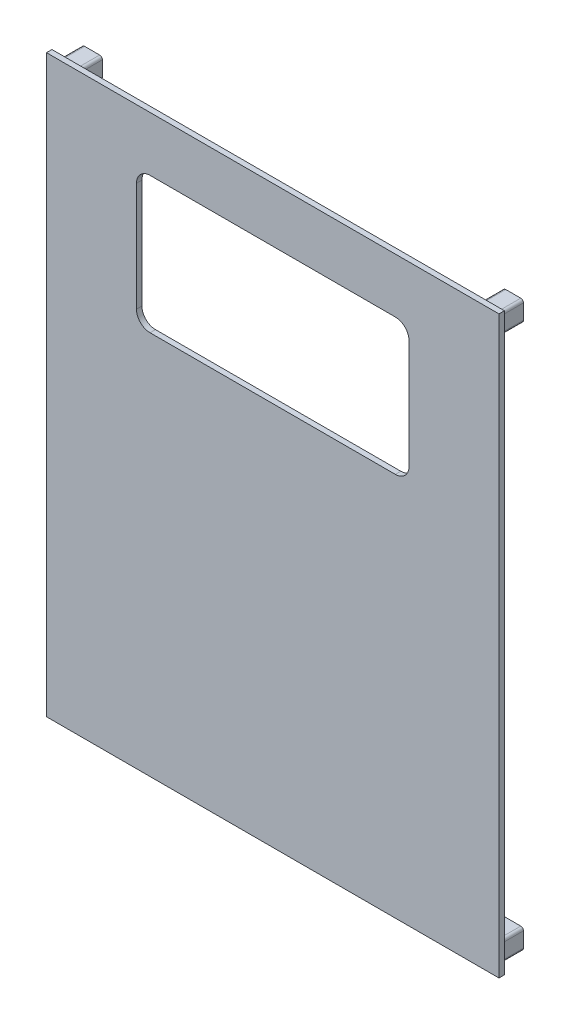
SolidWorks part; units mm, degrees
ref_plane "Front Plane" through (0, 0, 0) normal (0, 0, 1) x (1, 0, 0)
ref_plane "Top Plane" through (0, 0, 0) normal (0, 1, 0) x (1, 0, 0)
ref_plane "Right Plane" through (0, 0, 0) normal (1, 0, 0) x (0, 0, -1)
sketch "Sketch1" plane through (0, 0, 0) normal (0, 0, 1) x (1, 0, 0)
  line L4 (48, 73.2573) -> (48, -16.7427)
  line L5 (55, -23.7427) -> (105, -23.7427)
  line L6 (112, -16.7427) -> (112, 73.2573)
  line L7 (105, 80.2573) -> (55, 80.2573)
  line L8 (53, 73.2573) -> (53, -16.7427)
  line L9 (55, -18.7427) -> (105, -18.7427)
  line L10 (107, -16.7427) -> (107, 73.2573)
  line L11 (105, 75.2573) -> (55, 75.2573)
  arc A4 (48, -16.7427) -> (55, -23.7427) centre (55, -16.7427) ccw
  arc A5 (105, -23.7427) -> (112, -16.7427) centre (105, -16.7427) ccw
  arc A6 (112, 73.2573) -> (105, 80.2573) centre (105, 73.2573) ccw
  arc A7 (55, 80.2573) -> (48, 73.2573) centre (55, 73.2573) ccw
  arc A8 (53, -16.7427) -> (55, -18.7427) centre (55, -16.7427) ccw
  arc A9 (105, -18.7427) -> (107, -16.7427) centre (105, -16.7427) ccw
  arc A10 (107, 73.2573) -> (105, 75.2573) centre (105, 73.2573) ccw
  arc A11 (55, 75.2573) -> (53, 73.2573) centre (55, 73.2573) ccw
  dimension "D1" = 5
extrude "Boss-Extrude1" add sketch "Sketch1" against normal blind 3
sketch "Sketch2" plane through (0, 0, 0) normal (0, 0, 1) x (1, 0, 0)
  line L0 (-3, -127.7573) -> (163, -127.7573)
  line L1 (80, 83.2573) -> (80, -121.7427) construction
  line L3 (30, 63.2573) -> (130, 63.2573)
  line L6 (30, 63.2573) -> (30, 13.2573)
  line L9 (163, -127.7573) -> (163, 83.2573)
  line L10 (163, 83.2573) -> (-3, 83.2573)
  line L11 (-3, 83.2573) -> (-3, -127.7573)
  line L12 (30, 13.2573) -> (130, 13.2573)
  line L13 (130, 63.2573) -> (130, 13.2573)
extrude "Boss-Extrude2" add sketch "Sketch2" along normal blind 3
sketch "Sketch3" plane through (0, 0, -3) normal (0, 0, -1) x (-1, 0, 0)
  line L4 (-55, 80.2573) -> (-105, 80.2573)
  line L5 (-112, 73.2573) -> (-112, -16.7427)
  line L6 (-105, -23.7427) -> (-55, -23.7427)
  line L7 (-48, -16.7427) -> (-48, 73.2573)
  line L8 (-55, 80.2573) -> (-105, 80.2573)
  line L9 (-112, 73.2573) -> (-112, -16.7427)
  line L10 (-105, -23.7427) -> (-55, -23.7427)
  line L11 (-48, -16.7427) -> (-48, 73.2573)
  arc A4 (-48, 73.2573) -> (-55, 80.2573) centre (-55, 73.2573) ccw
  arc A5 (-105, 80.2573) -> (-112, 73.2573) centre (-105, 73.2573) ccw
  arc A6 (-112, -16.7427) -> (-105, -23.7427) centre (-105, -16.7427) ccw
  arc A7 (-55, -23.7427) -> (-48, -16.7427) centre (-55, -16.7427) ccw
  arc A8 (-48, 73.2573) -> (-55, 80.2573) centre (-55, 73.2573) ccw
  arc A9 (-105, 80.2573) -> (-112, 73.2573) centre (-105, 73.2573) ccw
  arc A10 (-112, -16.7427) -> (-105, -23.7427) centre (-105, -16.7427) ccw
  arc A11 (-55, -23.7427) -> (-48, -16.7427) centre (-55, -16.7427) ccw
  dimension "D1" = 0
extrude "Cut-Extrude1" cut sketch "Sketch3" against normal up to surface (3 mm away) up to face at (80, -22.25, 0)
fillet "Fillet1" radius 5 4 edges at (30, 63.2573, 1.5) (30, 13.2573, 1.5) (130, 13.2573, 1.5) (130, 63.2573, 1.5)
sketch "Sketch4" plane through (0, 0, 3) normal (0, 0, 1) x (1, 0, 0)
  line L4 (6.5, 81.2573) -> (-1, 81.2573)
  line L5 (6.5, 73.7573) -> (6.5, 81.2573)
  line L6 (-1, 73.7573) -> (6.5, 73.7573)
  line L7 (-1, 81.2573) -> (-1, 73.7573)
  line L8 (6.5, 81.2573) -> (-1, 81.2573)
  line L9 (6.5, 73.7573) -> (6.5, 81.2573)
  line L10 (-1, 73.7573) -> (6.5, 73.7573)
  line L11 (-1, 81.2573) -> (-1, 73.7573)
  line L12 (153.5, -125.7573) -> (161, -125.7573)
  line L13 (153.5, -118.2573) -> (153.5, -125.7573)
  line L14 (161, -118.2573) -> (153.5, -118.2573)
  line L15 (161, -125.7573) -> (161, -118.2573)
  line L16 (153.5, -125.7573) -> (161, -125.7573)
  line L17 (153.5, -118.2573) -> (153.5, -125.7573)
  line L18 (161, -118.2573) -> (153.5, -118.2573)
  line L19 (161, -125.7573) -> (161, -118.2573)
  line L20 (-1, -125.7573) -> (6.5, -125.7573)
  line L21 (6.5, -125.7573) -> (6.5, -118.2573)
  line L22 (6.5, -118.2573) -> (-1, -118.2573)
  line L23 (-1, -118.2573) -> (-1, -125.7573)
  line L24 (-1, -125.7573) -> (6.5, -125.7573)
  line L25 (6.5, -125.7573) -> (6.5, -118.2573)
  line L26 (6.5, -118.2573) -> (-1, -118.2573)
  line L27 (-1, -118.2573) -> (-1, -125.7573)
  line L28 (161, 81.2573) -> (153.5, 81.2573)
  line L29 (161, 73.7573) -> (161, 81.2573)
  line L30 (153.5, 73.7573) -> (161, 73.7573)
  line L31 (153.5, 81.2573) -> (153.5, 73.7573)
  line L32 (161, 81.2573) -> (153.5, 81.2573)
  line L33 (161, 73.7573) -> (161, 81.2573)
  line L34 (153.5, 73.7573) -> (161, 73.7573)
  line L35 (153.5, 81.2573) -> (153.5, 73.7573)
  dimension "D1" = 0
  dimension "D2" = 0
  dimension "D3" = 0
  dimension "D4" = 0
extrude "Boss-Extrude3" add sketch "Sketch4" against normal blind 11
fillet "Fillet2" radius 1 16 edges at (161, -118.2573, -4) (153.5, -118.2573, -4) (161, -125.7573, -4) (153.5, -125.7573, -4) (6.5, -125.7573, -4) (-1, -125.7573, -4) (6.5, -118.2573, -4) (-1, -118.2573, -4) (-1, 73.7573, -4) (-1, 81.2573, -4) (6.5, 81.2573, -4) (6.5, 73.7573, -4) (153.5, 73.7573, -4) (161, 73.7573, -4) (153.5, 81.2573, -4) (161, 81.2573, -4)
sketch "Sketch5" plane through (0, 0, -8) normal (0, 0, -1) x (-1, 0, 0)
  circle A0 centre (-157.25, 77.5073) radius 1.6
  circle A1 centre (-2.75, 77.5073) radius 1.6
  circle A2 centre (-2.75, -122.0073) radius 1.6
  circle A3 centre (-157.25, -122.0073) radius 1.6
extrude "Cut-Extrude2" cut sketch "Sketch5" against normal blind 5
sketch "Sketch6" plane through (0, 0, -8) normal (0, 0, -1) x (-1, 0, 0)
  circle A0 centre (-157.25, 77.5073) radius 2.25
  circle A1 centre (-2.75, 77.5073) radius 2.25
  circle A2 centre (-157.25, -122.0073) radius 2.25
  circle A3 centre (-2.75, -122.0073) radius 2.25
extrude "Cut-Extrude3" cut sketch "Sketch6" against normal blind 3
sketch "Sketch7" plane through (0, 0, 0) normal (0, 0, -1) x (-1, 0, 0)
  line L4 (3, -127.7573) -> (3, 83.2573)
  line L5 (3, 83.2573) -> (-163, 83.2573)
  line L6 (-163, 83.2573) -> (-163, -127.7573)
  line L7 (-163, -127.7573) -> (3, -127.7573)
  line L8 (3, -127.7573) -> (3, 83.2573)
  line L9 (3, 83.2573) -> (-163, 83.2573)
  line L10 (-163, 83.2573) -> (-163, -127.7573)
  line L11 (-163, -127.7573) -> (3, -127.7573)
  line L12 (-160, 73.7573) -> (-154.5, 73.7573)
  line L13 (-153.5, 74.7573) -> (-153.5, 80.2573)
  line L14 (-154.5, 81.2573) -> (-160, 81.2573)
  line L15 (-161, 80.2573) -> (-161, 74.7573)
  line L16 (-160, 73.7573) -> (-154.5, 73.7573)
  line L17 (-153.5, 74.7573) -> (-153.5, 80.2573)
  line L18 (-154.5, 81.2573) -> (-160, 81.2573)
  line L19 (-161, 80.2573) -> (-161, 74.7573)
  line L20 (-5.5, 73.7573) -> (0, 73.7573)
  line L21 (1, 74.7573) -> (1, 80.2573)
  line L22 (0, 81.2573) -> (-5.5, 81.2573)
  line L23 (-6.5, 80.2573) -> (-6.5, 74.7573)
  line L24 (-5.5, 73.7573) -> (0, 73.7573)
  line L25 (1, 74.7573) -> (1, 80.2573)
  line L26 (0, 81.2573) -> (-5.5, 81.2573)
  line L27 (-6.5, 80.2573) -> (-6.5, 74.7573)
  line L28 (-154.5, -118.2573) -> (-160, -118.2573)
  line L29 (-161, -119.2573) -> (-161, -124.7573)
  line L30 (-160, -125.7573) -> (-154.5, -125.7573)
  line L31 (-153.5, -124.7573) -> (-153.5, -119.2573)
  line L32 (-154.5, -118.2573) -> (-160, -118.2573)
  line L33 (-161, -119.2573) -> (-161, -124.7573)
  line L34 (-160, -125.7573) -> (-154.5, -125.7573)
  line L35 (-153.5, -124.7573) -> (-153.5, -119.2573)
  line L36 (-6.5, -119.2573) -> (-6.5, -124.7573)
  line L37 (-5.5, -125.7573) -> (0, -125.7573)
  line L38 (1, -124.7573) -> (1, -119.2573)
  line L39 (0, -118.2573) -> (-5.5, -118.2573)
  line L40 (-6.5, -119.2573) -> (-6.5, -124.7573)
  line L41 (-5.5, -125.7573) -> (0, -125.7573)
  line L42 (1, -124.7573) -> (1, -119.2573)
  line L43 (0, -118.2573) -> (-5.5, -118.2573)
  arc A4 (-154.5, 73.7573) -> (-153.5, 74.7573) centre (-154.5, 74.7573) ccw
  arc A5 (-153.5, 80.2573) -> (-154.5, 81.2573) centre (-154.5, 80.2573) ccw
  arc A6 (-160, 81.2573) -> (-161, 80.2573) centre (-160, 80.2573) ccw
  arc A7 (-161, 74.7573) -> (-160, 73.7573) centre (-160, 74.7573) ccw
  arc A8 (-154.5, 73.7573) -> (-153.5, 74.7573) centre (-154.5, 74.7573) ccw
  arc A9 (-153.5, 80.2573) -> (-154.5, 81.2573) centre (-154.5, 80.2573) ccw
  arc A10 (-160, 81.2573) -> (-161, 80.2573) centre (-160, 80.2573) ccw
  arc A11 (-161, 74.7573) -> (-160, 73.7573) centre (-160, 74.7573) ccw
  arc A12 (0, 73.7573) -> (1, 74.7573) centre (0, 74.7573) ccw
  arc A13 (1, 80.2573) -> (0, 81.2573) centre (0, 80.2573) ccw
  arc A14 (-5.5, 81.2573) -> (-6.5, 80.2573) centre (-5.5, 80.2573) ccw
  arc A15 (-6.5, 74.7573) -> (-5.5, 73.7573) centre (-5.5, 74.7573) ccw
  arc A16 (0, 73.7573) -> (1, 74.7573) centre (0, 74.7573) ccw
  arc A17 (1, 80.2573) -> (0, 81.2573) centre (0, 80.2573) ccw
  arc A18 (-5.5, 81.2573) -> (-6.5, 80.2573) centre (-5.5, 80.2573) ccw
  arc A19 (-6.5, 74.7573) -> (-5.5, 73.7573) centre (-5.5, 74.7573) ccw
  arc A20 (-160, -118.2573) -> (-161, -119.2573) centre (-160, -119.2573) ccw
  arc A21 (-161, -124.7573) -> (-160, -125.7573) centre (-160, -124.7573) ccw
  arc A22 (-154.5, -125.7573) -> (-153.5, -124.7573) centre (-154.5, -124.7573) ccw
  arc A23 (-153.5, -119.2573) -> (-154.5, -118.2573) centre (-154.5, -119.2573) ccw
  arc A24 (-160, -118.2573) -> (-161, -119.2573) centre (-160, -119.2573) ccw
  arc A25 (-161, -124.7573) -> (-160, -125.7573) centre (-160, -124.7573) ccw
  arc A26 (-154.5, -125.7573) -> (-153.5, -124.7573) centre (-154.5, -124.7573) ccw
  arc A27 (-153.5, -119.2573) -> (-154.5, -118.2573) centre (-154.5, -119.2573) ccw
  arc A28 (-6.5, -124.7573) -> (-5.5, -125.7573) centre (-5.5, -124.7573) ccw
  arc A29 (0, -125.7573) -> (1, -124.7573) centre (0, -124.7573) ccw
  arc A30 (1, -119.2573) -> (0, -118.2573) centre (0, -119.2573) ccw
  arc A31 (-5.5, -118.2573) -> (-6.5, -119.2573) centre (-5.5, -119.2573) ccw
  arc A32 (-6.5, -124.7573) -> (-5.5, -125.7573) centre (-5.5, -124.7573) ccw
  arc A33 (0, -125.7573) -> (1, -124.7573) centre (0, -124.7573) ccw
  arc A34 (1, -119.2573) -> (0, -118.2573) centre (0, -119.2573) ccw
  arc A35 (-5.5, -118.2573) -> (-6.5, -119.2573) centre (-5.5, -119.2573) ccw
  dimension "D1" = 0
  dimension "D2" = 0
  dimension "D3" = 0
  dimension "D4" = 0
  dimension "D5" = 0
extrude "Cut-Extrude4" cut sketch "Sketch7" against normal blind 1
